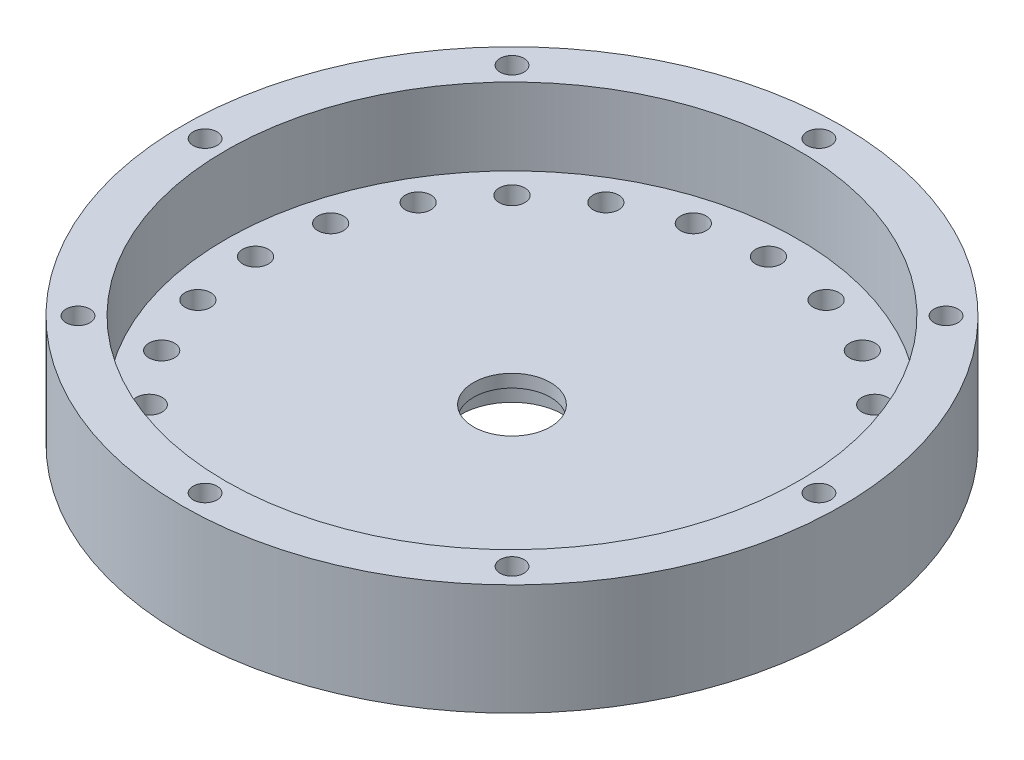
SolidWorks part; units mm, degrees
ref_plane "Front Plane" through (0, 0, 0) normal (0, 0, 1) x (1, 0, 0)
ref_plane "Top Plane" through (0, 0, 0) normal (0, 1, 0) x (1, 0, 0)
ref_plane "Right Plane" through (0, 0, 0) normal (1, 0, 0) x (0, 0, -1)
sketch "Sketch1" plane through (0, 0, 0) normal (0, 1, 0) x (1, 0, 0)
  circle A0 centre (0, 0) radius 77.1
  dimension "D1" = 154.2
extrude "Boss-Extrude1" add sketch "Sketch1" along normal blind 26
sketch "Sketch2" plane through (0, 26, 0) normal (0, 1, 0) x (1, 0, 0)
  circle A0 centre (0, 0) radius 67
  dimension "D1" = 134
extrude "Cut-Extrude1" cut sketch "Sketch2" against normal blind 18
sketch "Sketch3" plane through (0, 8, 0) normal (0, 1, 0) x (1, 0, 0)
  circle A1 centre (60, 0) radius 3
  circle A2 centre (57.9555, -15.5291) radius 3
  circle A3 centre (51.9615, -30) radius 3
  circle A4 centre (42.4264, -42.4264) radius 3
  circle A5 centre (30, -51.9615) radius 3
  circle A6 centre (15.5291, -57.9555) radius 3
  circle A7 centre (0, -60) radius 3
  circle A8 centre (-15.5291, -57.9555) radius 3
  circle A9 centre (-30, -51.9615) radius 3
  circle A10 centre (-42.4264, -42.4264) radius 3
  circle A11 centre (-51.9615, -30) radius 3
  circle A12 centre (-57.9555, -15.5291) radius 3
  circle A13 centre (-60, 0) radius 3
  circle A14 centre (-57.9555, 15.5291) radius 3
  circle A15 centre (-51.9615, 30) radius 3
  circle A16 centre (-42.4264, 42.4264) radius 3
  circle A17 centre (-30, 51.9615) radius 3
  circle A18 centre (-15.5291, 57.9555) radius 3
  circle A19 centre (0, 60) radius 3
  circle A20 centre (15.5291, 57.9555) radius 3
  circle A21 centre (30, 51.9615) radius 3
  circle A22 centre (42.4264, 42.4264) radius 3
  circle A27 centre (51.9615, 30) radius 3
  circle A28 centre (57.9555, 15.5291) radius 3
  point P13 (0, 0)
  dimension "D2" = 60
  dimension "D3" = 24
extrude "Cut-Extrude2" cut sketch "Sketch3" against normal blind 5
sketch "Sketch4" plane through (0, 0, 0) normal (0, -1, 0) x (1, 0, 0)
  circle A0 centre (0, 0) radius 12
  dimension "D1" = 24
extrude "Cut-Extrude3" cut sketch "Sketch4" against normal blind 5
sketch "Sketch5" plane through (0, 8, 0) normal (0, 1, 0) x (1, 0, 0)
  circle A0 centre (0, 0) radius 9
  dimension "D1" = 18
extrude "Cut-Extrude4" cut sketch "Sketch5" against normal blind 5
sketch "Sketch6" plane through (0, 26, 0) normal (0, 1, 0) x (1, 0, 0)
  line L0 (0, 71.8) -> (0, 0) construction
  circle A0 centre (0, 71.8) radius 2.8
  circle A3 centre (50.7703, 50.7703) radius 2.8
  circle A4 centre (71.8, 0) radius 2.8
  circle A5 centre (50.7703, -50.7703) radius 2.8
  circle A6 centre (0, -71.8) radius 2.8
  circle A7 centre (-50.7703, -50.7703) radius 2.8
  circle A8 centre (-71.8, 0) radius 2.8
  circle A9 centre (-50.7703, 50.7703) radius 2.8
  point P19 (0, 0)
  dimension "D3" = 71.8
  dimension "D2" = 8
extrude "Cut-Extrude5" cut sketch "Sketch6" against normal blind 8
equation "\"N_pin\"= 24"
equation "\"R_pin\"= 60"
equation "\"d_pin\"= 13"
equation "\"e\"= 1.5"
equation "\"t_disk\"= 5"
equation "\"N_outpin\"= 8"
equation "\"R_outpin\"= 34"
equation "\"d_outpin\"= 13"
equation "\"N_lobes\"= \"N_pin\" - 1"
equation "\"d_outhole\"= \"d_outpin\" + 2 * \"e\""
equation "\"ratio\"= \"N_lobes\""
equation "\"d_center\"= 24"
equation "\"a_hole1\"= 0 / \"N_lobes\""
equation "\"a_hole2\"= 360 / \"N_disk\" / \"N_lobes\""
equation "\"a_hole3\"= 720 / \"N_disk\" / \"N_lobes\""
equation "\"N_disk\"= 3"
equation "\"t_gap\"= 0.5"
equation "\"L_stack\"= \"N_disk\" * \"t_disk\" + (\"N_disk\" - 1) * \"t_gap\""
equation "\"d_pinshaft\"= 6"
equation "\"d_ecc\"= 15"
equation "\"d_outbrg\"= 47"
equation "\"w_outbrg\"= 7"
equation "\"d_outshaft\"= 35"
equation "\"w_brg\"= 5"
equation "\"c_run\"= 0.5"
equation "\"c_ax\"= 2 * \"t_gap\""
equation "\"D_pocket\"= 2 * \"R_pin\" + \"d_pin\" + 2 * \"c_run\""
equation "\"h_pocket\"= \"L_stack\" + 2 * \"c_ax\""
equation "\"t_floor\"= 8"
equation "\"d_insert\"= 5.6"
equation "\"N_bolt\"= 8"
equation "\"R_bolt\"= \"D_pocket\" / 2 + 2 + \"d_insert\" / 2"
equation "\"D_housing\"= 2 * (\"R_bolt\" + \"d_insert\" / 2 + 2.5)"
equation "\"D1@Sketch1\"=\"D_housing\""
equation "\"D1@Boss-Extrude1\"=\"t_floor\"+\"h_pocket\""
equation "\"D1@Sketch2\"=\"D_pocket\""
equation "\"D1@Cut-Extrude1\"=\"h_pocket\""
equation "\"D1@Sketch3\"=\"d_pinshaft\""
equation "\"D2@Sketch3\"=\"R_pin\""
equation "\"D1@Cut-Extrude2\"=\"t_floor\"-3"
equation "\"D3@Sketch3\"=\"N_pin\""
equation "\"D1@Sketch4\"=\"d_center\""
equation "\"D1@Cut-Extrude3\"=\"w_brg\""
equation "\"D1@Sketch5\"=\"d_ecc\"+3"
equation "\"D1@Sketch6\"=\"d_insert\""
equation "\"D2@Sketch6\"=\"N_bolt\""
equation "\"D3@Sketch6\"=\"R_bolt\""
